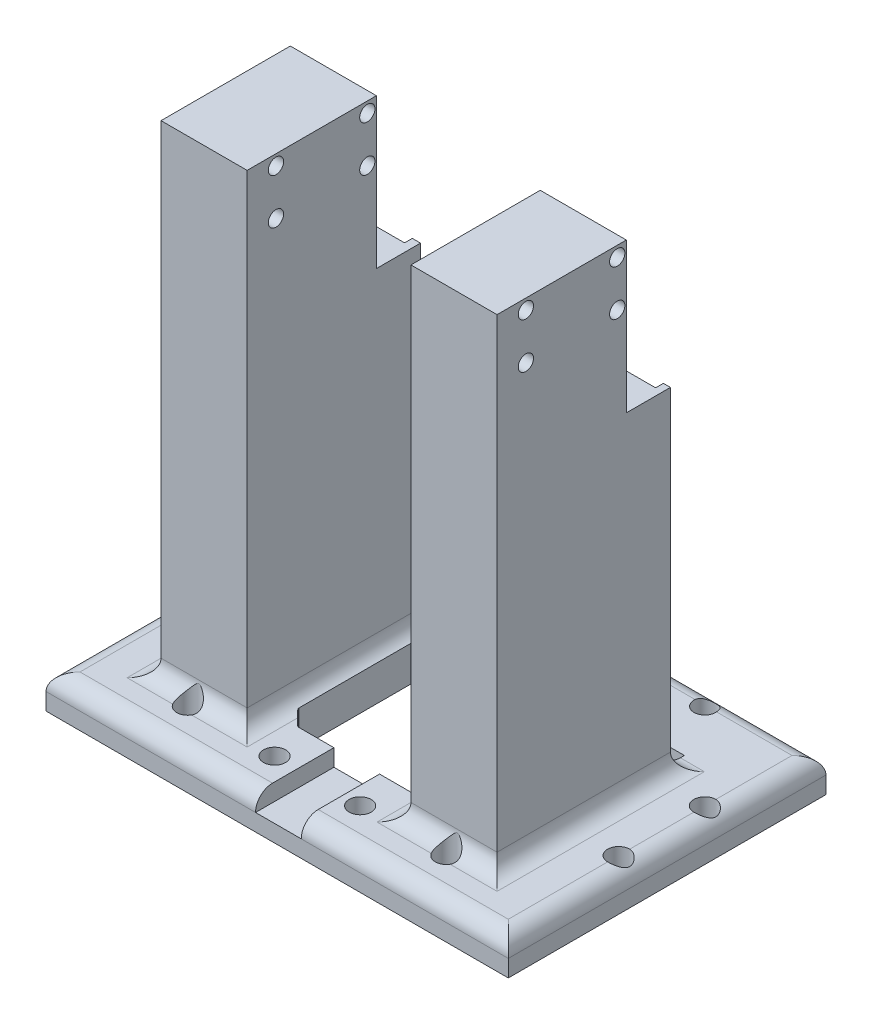
SolidWorks part; units mm, degrees
ref_plane "Front Plane" through (0, 0, 0) normal (0, 0, 1) x (1, 0, 0)
ref_plane "Top Plane" through (0, 0, 0) normal (0, 1, 0) x (1, 0, 0)
ref_plane "Right Plane" through (0, 0, 0) normal (1, 0, 0) x (0, 0, -1)
sketch "Sketch1" plane through (4645.495, -5615.4512, 222.287) normal (0, 1, 0) x (1, 0, 0)
  line L1 (-5.004, 249.919) -> (131.2605, 249.919)
  line L2 (-5.004, 249.919) -> (-5.004, 156.2902)
  line L4 (131.2605, 249.919) -> (131.2605, 156.2902)
  line L5 (-5.004, 156.2902) -> (63.1283, 156.2902)
  line L6 (63.1283, 156.2902) -> (131.2605, 156.2902)
extrude "Boss-Extrude1" add sketch "Sketch1" along normal blind 10
sketch "Sketch2" plane through (0, -5605.4512, 0) normal (0, 1, 0) x (1, 0, 0)
  line L0 (4708.449, 27.6321) -> (4708.449, -65.9968) construction
  line L1 (4658.9212, -50.5381) -> (4684.3037, -50.5381)
  line L2 (4658.9212, -50.5381) -> (4658.9212, 0.5715)
  line L3 (4658.9212, 0.5715) -> (4684.3037, 0.5715)
  line L4 (4684.3037, -50.5381) -> (4684.3037, 0.5715)
  line L6 (4640.4911, -65.9968) -> (4776.7555, -65.9968) construction
  line L7 (4732.5944, -50.5381) -> (4732.5944, 0.5715)
  line L8 (4757.9768, 0.5715) -> (4732.5944, 0.5715)
  line L9 (4757.9768, -50.5381) -> (4757.9768, 0.5715)
  line L10 (4757.9768, -50.5381) -> (4732.5944, -50.5381)
  line L11 (4640.4911, 27.6321) -> (4640.4911, -65.9968) construction
  dimension "D1" = 18.4301
  dimension "D2" = 43.8126
  dimension "D3" = 15.4587
  dimension "D4" = 66.5683
  dimension "D5" = 67.9579
extrude "Boss-Extrude2" add sketch "Sketch2" along normal blind 142.2321
sketch "Sketch3" plane through (0, 0, -0.5715) normal (0, 0, -1) x (-1, 0, 0)
  line L0 (-4737.0174, -5587.0652) -> (-4661.3426, -5587.0652) construction
  line L1 (-4661.3426, -5550.0756) -> (-4658.9212, -5550.0756) construction
  line L2 (-4661.3426, -5587.0652) -> (-4681.8823, -5587.0652)
  line L3 (-4661.3426, -5587.0652) -> (-4661.3426, -5463.2191)
  line L4 (-4661.3426, -5463.2191) -> (-4681.8823, -5463.2191)
  line L5 (-4681.8823, -5587.0652) -> (-4681.8823, -5463.2191)
  line L6 (-4658.9212, -5463.2191) -> (-4658.9212, -5605.4512) construction
  line L7 (-4681.8823, -5550.0756) -> (-4684.3037, -5550.0756) construction
  line L8 (-4684.3037, -5463.2191) -> (-4684.3037, -5605.4512) construction
  line L9 (-4684.3037, -5605.4512) -> (-4658.9212, -5605.4512) construction
  dimension "D1" = 2.4214
  dimension "D2" = 18.386
  dimension "D3" = 55.3755
  dimension "D4" = 142.2321
extrude "Cut-Extrude1" cut sketch "Sketch3" against normal blind 5.5
sketch "Sketch4" plane through (0, 0, 4.9285) normal (0, 0, -1) x (-1, 0, 0)
  line L0 (-4684.3037, -5463.2191) -> (-4684.3037, -5605.4512) construction
  line L1 (-4684.3037, -5507.3461) -> (-4658.9212, -5507.3461)
  line L2 (-4684.3037, -5507.3461) -> (-4684.3037, -5460.4819)
  line L3 (-4684.3037, -5460.4819) -> (-4658.9212, -5460.4819)
  line L4 (-4658.9212, -5507.3461) -> (-4658.9212, -5460.4819)
extrude "Cut-Extrude2" cut sketch "Sketch4" against normal blind 7.5 and the other way blind 12.5
fillet "Fillet14" radius 5 12 edges at (4745.2856, -5605.4512, -0.5715) (4732.5944, -5605.4512, 24.9833) (4745.2856, -5605.4512, 50.5381) (4757.9768, -5605.4512, 24.9833) (4684.3037, -5605.4512, 24.9833) (4671.6124, -5605.4512, -0.5715) (4658.9212, -5605.4512, 24.9833) (4671.6124, -5605.4512, 50.5381) (4708.6233, -5605.4512, -27.6321) (4776.7555, -5605.4512, 19.1824) (4708.6233, -5605.4512, 65.9968) (4640.4911, -5605.4512, 19.1824)
ref_plane "Plane1" through (4708.6233, 0, 0) normal (-1, 0, 0) x (0, 0, 1)
mirror "Mirror1" about plane through (4708.6233, 0, 0) normal (-1, 0, 0) of "Cut-Extrude1", "Cut-Extrude2"
sketch "Sketch5" plane through (0, 0, 4.9285) normal (0, 0, -1) x (-1, 0, 0)
  line L0 (-4661.3426, -5587.0652) -> (-4661.3426, -5507.3461) construction
  line L1 (-4661.3426, -5507.3461) -> (-4681.8823, -5507.3461) construction
  circle A0 centre (-4671.8428, -5574.7372) radius 1.6
  circle A1 centre (-4671.8428, -5528.736) radius 1.6
  circle A2 centre (-4745.0174, -5574.7372) radius 1.6
  circle A3 centre (-4745.0174, -5528.6285) radius 1.6
  dimension "D1" = 3.2
  dimension "D2" = 10.5002
  dimension "D3" = 83.6748
  dimension "D4" = 21.2824
  dimension "D5" = 21.3899
  dimension "D6" = 67.3911
extrude "Cut-Extrude3" cut sketch "Sketch5" against normal blind 5
sketch "Sketch6" plane through (0, -5615.4512, 0) normal (0, -1, 0) x (1, 0, 0)
  line L0 (4687.3481, 38.1501) -> (4687.3481, 5.4507)
  line L1 (4687.3481, 5.4507) -> (4687.3544, 5.3237)
  line L2 (4687.3544, 5.3237) -> (4687.3726, 5.2023)
  line L3 (4687.3726, 5.2023) -> (4687.4221, 5.0233)
  line L4 (4687.4221, 5.0233) -> (4687.4447, 4.9647)
  line L5 (4687.4447, 4.9647) -> (4687.5086, 4.8326)
  line L6 (4687.5086, 4.8326) -> (4687.5713, 4.7315)
  line L7 (4687.5713, 4.7315) -> (4687.6389, 4.6419)
  line L8 (4687.6389, 4.6419) -> (4687.72, 4.5526)
  line L9 (4687.72, 4.5526) -> (4687.845, 4.4277)
  line L10 (4687.845, 4.4277) -> (4691.1377, 1.135)
  line L11 (4691.1377, 1.135) -> (4691.2224, 1.0511)
  line L12 (4691.2224, 1.0511) -> (4691.2515, 1.0245)
  line L13 (4691.2515, 1.0245) -> (4691.2955, 0.9873)
  line L14 (4691.2955, 0.9873) -> (4691.3592, 0.9392)
  line L15 (4691.3592, 0.9392) -> (4691.4281, 0.8937)
  line L16 (4691.4281, 0.8937) -> (4691.5232, 0.8407)
  line L17 (4691.5232, 0.8407) -> (4691.6109, 0.7967)
  line L18 (4691.6109, 0.7967) -> (4691.844, 0.7303)
  line L19 (4691.844, 0.7303) -> (4691.8846, 0.7229)
  line L20 (4691.8846, 0.7229) -> (4692.0931, 0.7057)
  line L21 (4692.0931, 0.7057) -> (4724.7925, 0.7057)
  line L22 (4724.7925, 0.7057) -> (4724.9361, 0.7138)
  line L23 (4724.9361, 0.7138) -> (4725.0268, 0.7275)
  line L24 (4725.0268, 0.7275) -> (4725.101, 0.7437)
  line L25 (4725.101, 0.7437) -> (4725.1643, 0.7613)
  line L26 (4725.1643, 0.7613) -> (4725.2646, 0.7967)
  line L27 (4725.2646, 0.7967) -> (4725.3342, 0.827)
  line L28 (4725.3342, 0.827) -> (4725.3953, 0.8558)
  line L29 (4725.3953, 0.8558) -> (4725.4499, 0.8784)
  line L30 (4725.4499, 0.8784) -> (4725.4967, 0.9188)
  line L31 (4725.4967, 0.9188) -> (4725.5263, 0.9392)
  line L32 (4725.5263, 0.9392) -> (4729.1655, 4.5526)
  line L33 (4729.1655, 4.5526) -> (4729.2621, 4.661)
  line L34 (4729.2621, 4.661) -> (4729.2985, 4.7091)
  line L35 (4729.2985, 4.7091) -> (4729.3266, 4.7498)
  line L36 (4729.3266, 4.7498) -> (4729.347, 4.7816)
  line L37 (4729.347, 4.7816) -> (4729.3712, 4.8225)
  line L38 (4729.3712, 4.8225) -> (4729.3971, 4.8704)
  line L39 (4729.3971, 4.8704) -> (4729.4441, 4.9572)
  line L40 (4729.4441, 4.9572) -> (4729.4612, 5.0172)
  line L41 (4729.4612, 5.0172) -> (4729.4755, 5.0588)
  line L42 (4729.4755, 5.0588) -> (4729.496, 5.1286)
  line L43 (4729.496, 5.1286) -> (4729.5163, 5.1981)
  line L44 (4729.5163, 5.1981) -> (4729.5197, 5.2391)
  line L45 (4729.5197, 5.2391) -> (4729.5433, 5.4507)
  line L46 (4729.5433, 5.4507) -> (4729.5375, 38.0901)
  line L47 (4729.5375, 38.0901) -> (4729.5433, 38.1501)
  line L48 (4729.5433, 38.1501) -> (4729.5349, 38.2308)
  line L49 (4729.5349, 38.2308) -> (4729.5015, 38.4775)
  line L50 (4729.5015, 38.4775) -> (4729.3712, 38.7905)
  line L51 (4729.3712, 38.7905) -> (4729.2753, 38.9228)
  line L52 (4729.2753, 38.9228) -> (4729.1764, 39.0593)
  line L53 (4729.1764, 39.0593) -> (4725.6905, 42.5231)
  line L54 (4725.6905, 42.5231) -> (4725.5513, 42.6435)
  line L55 (4725.5513, 42.6435) -> (4725.4373, 42.7284)
  line L56 (4725.4373, 42.7284) -> (4725.1256, 42.8575)
  line L57 (4725.1256, 42.8575) -> (4724.7925, 42.9095)
  line L58 (4724.7925, 42.9095) -> (4692.1742, 42.8951)
  line L59 (4692.1742, 42.8951) -> (4691.7584, 42.8646)
  line L60 (4691.7584, 42.8646) -> (4691.4548, 42.7388)
  line L61 (4691.4548, 42.7388) -> (4691.1825, 42.5364)
  line L62 (4691.1825, 42.5364) -> (4687.72, 39.0481)
  line L63 (4687.72, 39.0481) -> (4687.4974, 38.7905)
  line L64 (4687.4974, 38.7905) -> (4687.3726, 38.4893)
  line L65 (4687.3726, 38.4893) -> (4687.3481, 38.1501)
  line L68 (4640.4911, -27.6321) -> (4640.4911, 65.9968) construction
  line L69 (4776.7555, -27.6321) -> (4640.4911, -27.6321) construction
  dimension "D1" = 46.857
  dimension "D2" = 46.8634
  dimension "D3" = 46.8815
  dimension "D4" = 46.9311
  dimension "D5" = 46.9537
  dimension "D6" = 47.0063
  dimension "D7" = 47.0175
  dimension "D8" = 47.0802
  dimension "D9" = 47.1478
  dimension "D10" = 47.229
  dimension "D11" = 47.3539
  dimension "D12" = 50.6466
  dimension "D13" = 50.6914
  dimension "D14" = 50.7313
  dimension "D15" = 50.7604
  dimension "D16" = 50.8045
  dimension "D17" = 50.8681
  dimension "D18" = 50.937
  dimension "D19" = 50.9637
  dimension "D20" = 51.0322
  dimension "D21" = 51.1198
  dimension "D22" = 51.2674
  dimension "D23" = 51.3529
  dimension "D24" = 51.3935
  dimension "D25" = 51.602
  dimension "D26" = 51.6831
  dimension "D27" = 84.3014
  dimension "D28" = 84.445
  dimension "D29" = 84.5357
  dimension "D30" = 84.61
  dimension "D31" = 84.6346
  dimension "D32" = 84.6733
  dimension "D33" = 84.7735
  dimension "D34" = 84.8432
  dimension "D35" = 84.9042
  dimension "D36" = 84.9462
  dimension "D37" = 84.9589
  dimension "D38" = 85.0056
  dimension "D39" = 85.0353
  dimension "D40" = 85.0602
  dimension "D41" = 85.1994
  dimension "D42" = 88.6744
  dimension "D43" = 88.6853
  dimension "D44" = 88.7711
  dimension "D45" = 88.7843
  dimension "D46" = 88.8074
  dimension "D47" = 88.8355
  dimension "D48" = 88.8559
  dimension "D49" = 88.8802
  dimension "D50" = 88.9061
  dimension "D51" = 88.953
  dimension "D52" = 88.9701
  dimension "D53" = 88.9844
  dimension "D54" = 89.0049
  dimension "D55" = 89.0104
  dimension "D56" = 89.0252
  dimension "D57" = 89.0287
  dimension "D58" = 89.0438
  dimension "D59" = 89.0464
  dimension "D60" = 89.0523
  dimension "D61" = 28.3377
  dimension "D62" = 28.3459
  dimension "D63" = 28.355
  dimension "D64" = 28.3595
  dimension "D65" = 28.3624
  dimension "D66" = 28.3758
  dimension "D67" = 28.3934
  dimension "D68" = 28.4287
  dimension "D69" = 28.4591
  dimension "D70" = 28.4727
  dimension "D71" = 28.4879
  dimension "D72" = 28.5105
  dimension "D73" = 28.5257
  dimension "D74" = 28.5509
  dimension "D75" = 28.5712
  dimension "D76" = 28.6194
  dimension "D77" = 28.6566
  dimension "D78" = 28.6831
  dimension "D79" = 28.7671
  dimension "D80" = 32.0598
  dimension "D81" = 32.4545
  dimension "D82" = 32.274
  dimension "D83" = 32.2931
  dimension "D84" = 32.3412
  dimension "D85" = 32.3635
  dimension "D86" = 32.3818
  dimension "D87" = 32.4137
  dimension "D88" = 32.5024
  dimension "D89" = 32.4647
  dimension "D90" = 32.6908
  dimension "D91" = 32.7607
  dimension "D92" = 32.5967
  dimension "D93" = 32.6492
  dimension "D94" = 32.6554
  dimension "D95" = 32.8343
  dimension "D96" = 33.0827
  dimension "D97" = 66.1214
  dimension "D98" = 66.4226
  dimension "D99" = 32.8712
  dimension "D100" = 32.9558
  dimension "D101" = 66.5549
  dimension "D102" = 65.7222
  dimension "D103" = 66.6802
  dimension "D104" = 65.8629
  dimension "D105" = 66.1095
  dimension "D106" = 70.1552
  dimension "D107" = 70.3605
  dimension "D112" = 70.1685
  dimension "D115" = 70.3709
  dimension "D117" = 70.4967
  dimension "D118" = 70.5271
  dimension "D119" = 70.5416
extrude "Cut-Extrude4" cut sketch "Sketch6" against normal through all
sketch "Sketch7" plane through (0, -5605.4512, 0) normal (0, 1, 0) x (1, 0, 0)
  line L0 (4692.1742, -42.8951) -> (4724.7925, -42.9095) construction
  line L1 (4702.2489, -42.8995) -> (4715.713, -42.8995)
  line L2 (4702.2489, -42.8995) -> (4702.2489, -65.9968)
  line L3 (4702.2489, -65.9968) -> (4715.713, -65.9968)
  line L4 (4715.713, -42.8995) -> (4715.713, -65.9968)
  line L5 (4776.7555, -65.9968) -> (4640.4911, -65.9968) construction
  line L6 (4653.9212, -55.5381) -> (4653.9212, 5.5715) construction
  dimension "D1" = 48.3277
  dimension "D2" = 61.7918
extrude "Cut-Extrude5" cut sketch "Sketch7" against normal blind 5
sketch "Sketch8" plane through (0, -5615.4512, 0) normal (0, -1, 0) x (1, 0, 0)
  line L0 (4687.3481, 38.1501) -> (4687.3481, 5.4507) construction
  circle A0 centre (4670.1499, 53.8638) radius 3.25
  circle A1 centre (4746.3499, 53.8638) radius 3.25
  circle A2 centre (4720.9499, 53.8638) radius 3.25
  circle A3 centre (4670.1499, -22.3362) radius 3.25
  circle A4 centre (4695.6719, 53.8142) radius 3.25
  circle A5 centre (4695.5499, -22.3362) radius 3.25
  circle A6 centre (4720.9499, -22.3362) radius 3.25
  circle A7 centre (4746.3499, -22.3362) radius 3.175
  circle A8 centre (4771.7499, 28.4638) radius 3.25
  circle A9 centre (4771.7499, 3.0638) radius 3.25
  circle A10 centre (4644.7499, 3.0638) radius 3.25
  circle A11 centre (4644.7499, 28.4638) radius 3.25
  dimension "D1" = 6.5
  dimension "D2" = 6.5
  dimension "D3" = 6.5
  dimension "D4" = 6.5
  dimension "D5" = 6.5
  dimension "D6" = 6.5
  dimension "D7" = 6.5
  dimension "D8" = 6.35
  dimension "D9" = 6.5
  dimension "D10" = 6.5
  dimension "D11" = 6.5
  dimension "D12" = 6.5
  dimension "D13" = 8.2019
  dimension "D14" = 8.3239
  dimension "D15" = 33.6019
  dimension "D16" = 59.0019
  dimension "D17" = 84.4019
  dimension "D18" = 17.1981
  dimension "D19" = 42.5981
  dimension "D20" = 15.3248
  dimension "D21" = 15.3744
  dimension "D22" = 10.0256
  dimension "D23" = 35.4256
  dimension "D24" = 60.8256
extrude "Cut-Extrude6" cut sketch "Sketch8" against normal through all
sketch "Sketch14" plane through (4658.9212, 0, 0) normal (-1, 0, 0) x (0, 0, 1)
  circle A0 centre (15.1109, -5466.3255) radius 2.25
  circle A1 centre (15.1109, -5479.7251) radius 2.25
  circle A2 centre (42.0393, -5479.7251) radius 2.25
  circle A3 centre (42.0393, -5466.3255) radius 2.25
  dimension "D1" = 4.5
extrude "Cut-Extrude7" cut sketch "Sketch14" against normal through all
sketch "Sketch18" plane through (0, 0, 12.4285) normal (0, 0, -1) x (-1, 0, 0)
  line L0 (-4732.5944, -5463.2191) -> (-4732.5944, -5600.4512) construction
  line L1 (-4757.9768, -5463.2191) -> (-4732.5944, -5463.2191)
  line L2 (-4757.9768, -5463.2191) -> (-4757.9768, -5507.3461)
  line L3 (-4757.9768, -5507.3461) -> (-4732.5944, -5507.3461)
  line L4 (-4732.5944, -5463.2191) -> (-4732.5944, -5507.3461)
  line L5 (-4757.9768, -5507.3461) -> (-4757.9768, -5463.2191) construction
  line L6 (-4732.9429, -5507.3461) -> (-4757.9768, -5507.3461) construction
extrude "Cut-Extrude10" cut sketch "Sketch18" along normal through all
sketch "Sketch19" plane through (0, 0, -0.5715) normal (0, 0, -1) x (-1, 0, 0)
  line L0 (-4684.3037, -5600.4512) -> (-4658.9212, -5600.4512) construction
  line L1 (-4681.8823, -5587.0652) -> (-4661.3426, -5587.0652)
  line L2 (-4681.8823, -5587.0652) -> (-4681.8823, -5600.4512)
  line L3 (-4681.8823, -5600.4512) -> (-4661.3426, -5600.4512)
  line L4 (-4661.3426, -5587.0652) -> (-4661.3426, -5600.4512)
  line L5 (-4661.3426, -5587.0652) -> (-4661.3426, -5507.3461) construction
extrude "Cut-Extrude11" cut sketch "Sketch19" against normal up to surface (5.5 mm away) up to face at (4670.2428, -5528.736, 4.9285)
sketch "Sketch20" plane through (0, 0, -0.5715) normal (0, 0, -1) x (-1, 0, 0)
  line L0 (-4757.9768, -5600.4512) -> (-4732.5944, -5600.4512) construction
  line L1 (-4755.904, -5587.0652) -> (-4735.3643, -5587.0652)
  line L2 (-4755.904, -5587.0652) -> (-4755.904, -5600.4512)
  line L3 (-4755.904, -5600.4512) -> (-4735.3643, -5600.4512)
  line L4 (-4735.3643, -5587.0652) -> (-4735.3643, -5600.4512)
  line L5 (-4735.3643, -5507.3461) -> (-4735.3643, -5587.0652) construction
extrude "Cut-Extrude12" cut sketch "Sketch20" against normal up to surface (5.5 mm away) up to face at (4743.4174, -5574.7372, 4.9285)
sketch "Sketch21" plane through (0, 0, 4.9285) normal (0, 0, -1) x (-1, 0, 0)
  line L0 (-4755.904, -5507.3461) -> (-4735.3643, -5507.3461) construction
  line L1 (-4755.904, -5507.3461) -> (-4735.3643, -5507.3461)
  line L2 (-4755.904, -5507.3461) -> (-4755.904, -5600.4512)
  line L3 (-4755.904, -5600.4512) -> (-4735.3643, -5600.4512)
  line L4 (-4735.3643, -5507.3461) -> (-4735.3643, -5600.4512)
  line L5 (-4681.8823, -5507.3461) -> (-4661.3426, -5507.3461)
  line L6 (-4681.8823, -5507.3461) -> (-4681.8823, -5600.4512)
  line L7 (-4681.8823, -5600.4512) -> (-4661.3426, -5600.4512)
  line L8 (-4661.3426, -5507.3461) -> (-4661.3426, -5600.4512)
  circle A0 centre (-4745.0174, -5574.7372) radius 1.6
  circle A1 centre (-4745.0174, -5528.6285) radius 1.6
  circle A2 centre (-4671.8428, -5574.7372) radius 1.6
  circle A3 centre (-4671.8428, -5528.736) radius 1.6
  dimension "D1" = 3.2
extrude "Boss-Extrude3" add sketch "Sketch21" along normal blind 3.2069
sketch "Sketch22" plane through (0, -5600.4512, 0) normal (0, 1, 0) x (1, 0, 0)
  line L1 (4661.3426, -1.7216) -> (4681.8823, -1.7216)
  line L2 (4661.3426, -1.7216) -> (4661.3426, 6.7649)
  line L3 (4661.3426, 6.7649) -> (4681.8823, 6.7649)
  line L4 (4681.8823, -1.7216) -> (4681.8823, 6.7649)
extrude "Cut-Extrude13" cut sketch "Sketch22" against normal through all
sketch "Sketch23" plane through (0, -5600.4512, 0) normal (0, 1, 0) x (1, 0, 0)
  line L1 (4755.904, -1.7216) -> (4735.3643, -1.7216)
  line L2 (4755.904, -1.7216) -> (4755.904, 6.7649)
  line L3 (4755.904, 6.7649) -> (4735.3643, 6.7649)
  line L4 (4735.3643, -1.7216) -> (4735.3643, 6.7649)
extrude "Cut-Extrude14" cut sketch "Sketch23" against normal through all
